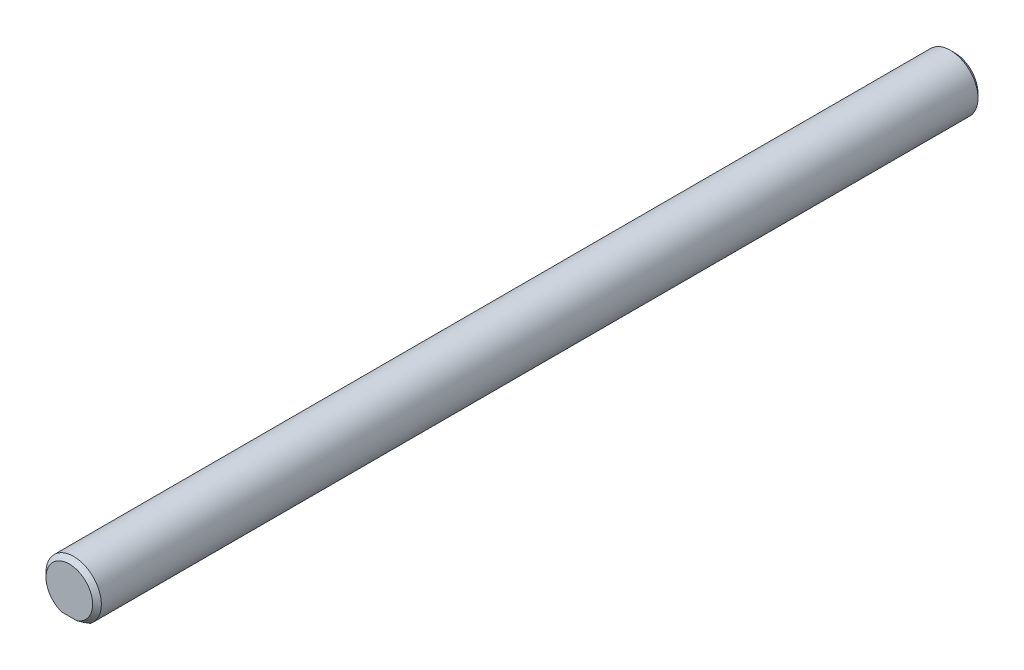
SolidWorks part; units mm, degrees
ref_plane "Front" through (0, 0, 0) normal (0, 0, 1) x (1, 0, 0)
ref_plane "Top" through (0, 0, 0) normal (0, 1, 0) x (1, 0, 0)
ref_plane "Right" through (0, 0, 0) normal (1, 0, 0) x (0, 0, -1)
sketch "Sketch1" plane through (0, 0, 0) normal (0, 0, 1) x (1, 0, 0)
  line L0 (-1.905, -2.54) -> (1.905, -2.54)
  circle A0 centre (0, 0) radius 3.175 construction
  arc A1 (-1.905, -2.54) -> (1.905, -2.54) centre (0, 0) cw
  dimension "D1" = 6.35
  dimension "D2" = 5.715
sketch "Sketch2" plane through (0, 0, 0) normal (0, 1, 0) x (1, 0, 0)
  line L0 (0, -50.8) -> (0, 50.8)
  point P3 (0, 0)
  dimension "D1" = 101.6
sweep "Sweep1" add profiles "Sketch1" path "Sketch2"
chamfer "Chamfer1" distance 0.5 angle 45 2 edges at (0, 3.175, -50.8) (0, 3.175, 50.8)
ref_axis "Axis1" through (0, 0, -50.3) along (0, 0, 1)
